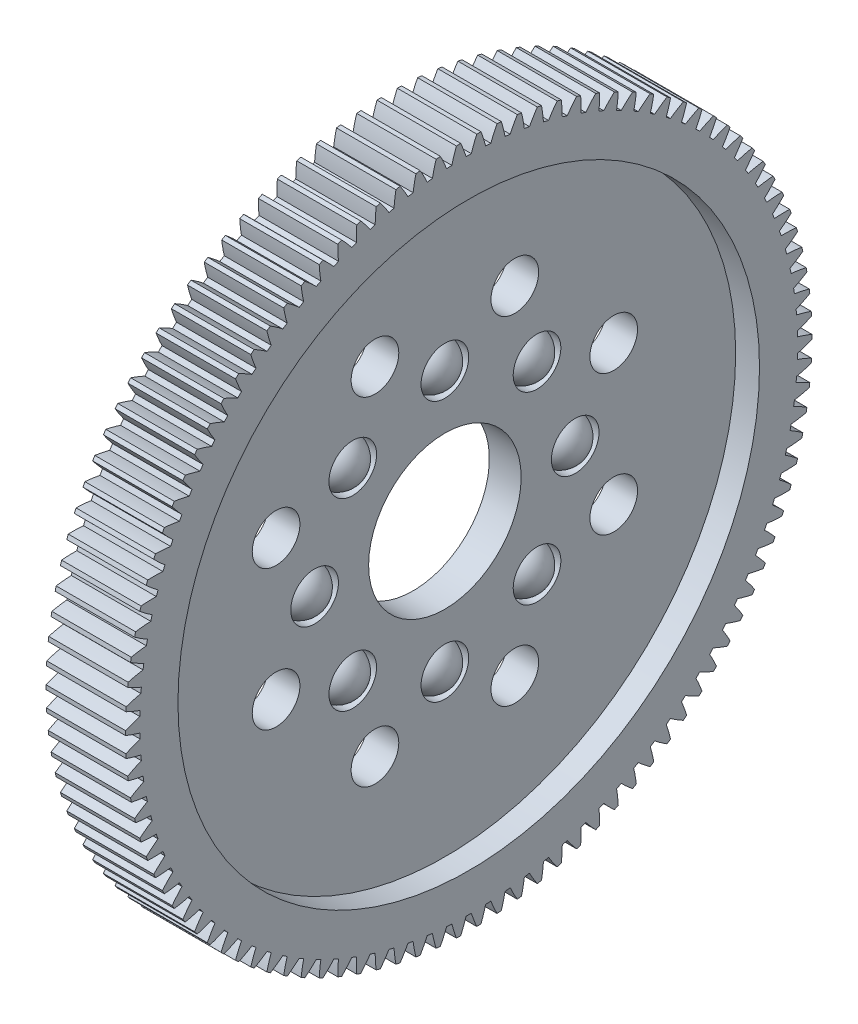
SolidWorks part; units mm, degrees
ref_plane "Plane1" through (0, 0, 0) normal (0, 0, 1) x (1, 0, 0)
ref_plane "Plane2" through (0, 0, 0) normal (0, 1, 0) x (1, 0, 0)
ref_plane "Plane3" through (0, 0, 0) normal (1, 0, 0) x (0, 0, -1)
sketch "HoldingSke" plane through (0, 0, 0) normal (0, 1, 0) x (1, 0, 0)
  line L0 (0, 0) -> (-0.6891, -2.4032)
  line L1 (-15, 0) -> (100, 0) construction
  line L2 (0, 0) -> (-2.1039, 2.3779)
  line L3 (0, 0) -> (-11.863, 4.5341)
  line L4 (0, 0) -> (-2.3804, 8.3015)
  line L5 (0, 0) -> (-46.8476, -17.4728)
  line L6 (0, 0) -> (-4.1448, -2.7965)
  line L7 (-2.1039, 2.3779) -> (8.6586, 51.2059)
  line L8 (-76.2, 54.61) -> (-76.1, 54.61)
  line L9 (-71.009, 38.7566) -> (-53.1078, 45.2721)
  line L10 (-76.2, 71.12) -> (104.1128, 71.12)
  line L11 (0, 0) -> (-5, 0)
  line L12 (-76.2, 101.6) -> (-76.185, 101.6)
  line L13 (24.9733, 27.94) -> (52.9518, 28.4284)
  line L14 (24.9733, 27.94) -> (24.9743, 27.94)
  line L15 (24.9733, 27.94) -> (100.4006, 29.5858)
  line L16 (-63.627, -0.4) -> (-12.827, -0.4)
  circle A0 centre (0, 0) radius 0.4
  circle A1 centre (0, 0) radius 20.699
  circle A2 centre (0, 0) radius 37.5
  circle A3 centre (0, 0) radius 0.4
  dimension "MHD" = 41.398
  dimension "Hub_dia" = 75
  dimension "Bore" = 0.8
  dimension "MBD" = 0.8
  dimension "Num_teeth" = 106
  dimension "Pitch_radius" = 180.3128
  dimension "Pitch" = 2.5
  dimension "Width" = 5
  dimension "Overall_len" = 50
  dimension "Show_teeth" = 106
  dimension "Thickness" = 5
  dimension "OAL" = 50.0001
  dimension "T_dim" = 0.1
  dimension "Ap" = 20
  dimension "H" = 19.05
  dimension "Backlash" = 0.015
  dimension "Addendum_fac" = 1
  dimension "Dedendum_fac" = 1.25
  dimension "Clearance_fac" = 0.25
  dimension "Dedendum_add" = 0.001
  dimension "Module" = 0.4
sketch "BasProSke" plane through (0, 0, 0) normal (0, 1, 0) x (1, 0, 0)
  line L0 (-10, 0) -> (60, 0) construction
  line L1 (0, 0) -> (0, 21.6)
  line L2 (0, 0) -> (5, 0)
  line L3 (5, 0) -> (5, 21.6)
  line L4 (5, 21.6) -> (0, 21.6)
  dimension "Diameter" = 43.2
  dimension "Thickness" = 5
revolve "Base-Revolve" add sketch "BasProSke" angle 360 about L0
sketch "TooCutSke" plane through (0, 0, 0) normal (1, 0, 0) x (0, 0, -1)
  line L1 (0, 0) -> (0, 107) construction
  line L2 (0, 0) -> (-0.3404, 21.1973) construction
  line L3 (0, 0) -> (-1.2563, 42.3775) construction
  line L4 (-0.3404, 21.1973) -> (-0.6282, 21.1887) construction
  arc A0 (0.1648, 20.6983) -> (-0.1648, 20.6983) centre (0, 0) ccw
  arc A1 (0.5171, 21.6192) -> (-0.5171, 21.6192) centre (0, 0) ccw
  circle A2 centre (0, 0) radius 21.2 construction
  circle A3 centre (0, 0) radius 19.9215 construction
  arc A4 (-0.1648, 20.6983) -> (-0.5171, 21.6192) centre (-8.2478, 18.1339) ccw
  arc A5 (0.5171, 21.6192) -> (0.1648, 20.6983) centre (8.2478, 18.1339) ccw
  dimension "Root_dia" = 41.398
  dimension "Overcut_dia" = 43.2508
  dimension "Pitch_dia" = 42.4
  dimension "Base_dia" = 39.843
  dimension "Flank_rad" = 8.48
  dimension "Half_ang" = 1.698
  dimension "Half_CT" = 0.2879
extrude "ToothCut" cut sketch "TooCutSke" along normal through all
fillet "Breaks" [suppressed] radius 0.008 tangent propagation no
fillet "RootFillets" [suppressed] radius 0.101
pattern_circular "TeethCuts" count 106 over 360 about axis through (-10, 0, 0) along (1, 0, 0) of "ToothCut", "RootFillets", "Breaks"
sketch "HubNeaOneSke" plane through (0, 0, 0) normal (-1, 0, 0) x (0, 0, 1)
  circle A0 centre (0, 0) radius 20.699
  dimension "Diameter" = 41.398
extrude "HubNearOne" [suppressed] add sketch "HubNeaOneSke" along normal blind 45.0001
sketch "HubNeaBotSke" plane through (0, 0, 0) normal (-1, 0, 0) x (0, 0, 1)
  circle A0 centre (0, 0) radius 20.699
  dimension "Diameter" = 41.398
extrude "HubNearBoth" [suppressed] add sketch "HubNeaBotSke" along normal blind 22.5
ref_plane "FarPln" through (5, 0, 0) normal (1, 0, 0) x (0, 0, -1)
sketch "HubFarSke" plane through (5, 0, 0) normal (1, 0, 0) x (0, 0, -1)
  circle A0 centre (0, 0) radius 20.699
  dimension "Diameter" = 41.398
extrude "HubFar" [suppressed] add sketch "HubFarSke" along normal blind 22.5
sketch "BorSke" plane through (0, 0, 0) normal (1, 0, 0) x (0, 0, -1)
  circle A0 centre (0, 0) radius 4.8
  dimension "Diameter" = 9.6
extrude "Bore" cut sketch "BorSke" along normal mid plane 100.0001
sketch "KeySke" plane through (0, 0, 0) normal (1, 0, 0) x (0, 0, -1)
  line L0 (-0.05, 0) -> (-0.05, 0.5)
  line L1 (-0.05, 0.5) -> (0.05, 0.5)
  line L2 (0.05, 0.5) -> (0.05, 0)
  line L3 (0, 0) -> (0, 34) construction
  line L4 (-0.05, 0) -> (0.05, 0)
  dimension "Offset" = 0.5
  dimension "Width" = 0.1
extrude "Keyway" [suppressed] cut sketch "KeySke" along normal mid plane 100.0001
pattern_circular "Keyway2" [suppressed] count 2 every 90 about axis through (-10, 0, 0) along (1, 0, 0)
ref_plane "Plane4" through (2.5, 0, 0) normal (1, 0, 0) x (0, 0, -1)
ref_axis "Axis1" through (-80.9, 0, 0) along (1, 0, 0)
sketch "Sketch2" plane through (5, 0, 0) normal (1, 0, 0) x (0, 0, -1)
  circle A0 centre (0, 0) radius 18.3
  dimension "D1" = 36.6
extrude "Cut-Extrude1" cut sketch "Sketch2" against normal blind 1.5
mirror "Mirror1" about plane through (2.5, 0, 0) normal (1, 0, 0) of "Cut-Extrude1"
sketch "Sketch3" plane through (2.5, 0, 0) normal (1, 0, 0) x (0, 0, -1)
  line L0 (0, 0) -> (0, 13.0334) construction
  line L1 (0, 0) -> (-5.791, 13.9807) construction
  circle A1 centre (0, 8.2) radius 1.5
  circle A2 centre (5.7983, 5.7983) radius 1.5
  circle A3 centre (8.2, 0) radius 1.5
  circle A4 centre (5.7983, -5.7983) radius 1.5
  circle A5 centre (0, -8.2) radius 1.5
  circle A6 centre (-5.7983, -5.7983) radius 1.5
  circle A7 centre (-8.2, 0) radius 1.5
  circle A8 centre (-5.7983, 5.7983) radius 1.5
  circle A9 centre (-4.4009, 10.6246) radius 1.5
  circle A10 centre (4.4009, 10.6246) radius 1.5
  circle A11 centre (10.6246, 4.4009) radius 1.5
  circle A12 centre (10.6246, -4.4009) radius 1.5
  circle A13 centre (4.4009, -10.6246) radius 1.5
  circle A14 centre (-4.4009, -10.6246) radius 1.5
  circle A15 centre (-10.6246, -4.4009) radius 1.5
  circle A16 centre (-10.6246, 4.4009) radius 1.5
  point P22 (0, 0)
  point P40 (0, 0)
  dimension "D3" = 3
  dimension "D6" = 3
  dimension "D2" = 8.2
  dimension "D5" = 22.5
  dimension "D7" = 11.5
  dimension "D4" = 8
  dimension "D8" = 8
extrude "Cut-Extrude2" cut sketch "Sketch3" against normal up to next and the other way up to next
sketch "Sketch4" plane through (2.5, 0, 0) normal (1, 0, 0) x (0, 0, -1)
  line L0 (0, 9.701) -> (0, 6.699)
  arc A0 (0, 6.699) -> (0, 9.701) centre (0, 8.2) ccw
  dimension "D1" = 1.501
revolve "Revolve1" add sketch "Sketch4" angle 360 about L0
pattern_circular "CirPattern3" count 8 over 360 about axis through (-80.9, 0, 0) along (1, 0, 0) of "Revolve1"
equation "' \"Module@HoldingSke\" = 6.35"
equation "' \"Num_teeth@HoldingSke\" = 12"
equation "' \"Ap@HoldingSke\" =  20"
equation "' \"Width@HoldingSke\" = 0.5 * 25.4"
equation "' \"Hub_dia@HoldingSke\"= 1 * 25.4"
equation "' \"Overall_len@HoldingSke\" = 1.0 * 25.4"
equation "' \"Bore@HoldingSke\" = 0.75 * 25.4"
equation "' \"T_dim@HoldingSke\" = 0.1 * 25.4"
equation "' \"Width@KeySke\" = 0.25 * 25.4"
equation "' \"Show_teeth@HoldingSke\" = 13"
equation "' \"Backlash@HoldingSke\" = 0.009 * 25.4"
equation "' \"Addendum_fac@HoldingSke\" = 1.0"
equation "' \"Dedendum_fac@HoldingSke\" = 1.25"
equation "' \"Dedendum_add@HoldingSke\" = 0.00005 * 25.4"
equation "' \"Clearance_fac@HoldingSke\" = 0.25"
equation "\"Pitch@HoldingSke\" = 1 / \"Module@HoldingSke\""
equation "\"Overcut_dia@TooCutSke\" = (\"Num_teeth@HoldingSke\" + 2 * \"Addendum_fac@HoldingSke\") / \"Pitch@HoldingSke\" + 0.002 * 25.4"
equation "\"Pitch_dia@TooCutSke\" = \"Num_teeth@HoldingSke\" / \"Pitch@HoldingSke\""
equation "\"Base_dia@TooCutSke\" = \"Num_teeth@HoldingSke\" / \"Pitch@HoldingSke\" * cos((\"Ap@HoldingSke\"  * 3.14159265 / 180))"
equation "\"Root_dia@TooCutSke\" = (\"Num_teeth@HoldingSke\" + 2) / \"Pitch@HoldingSke\" - 2 * (\"Addendum_fac@HoldingSke\" + \"Dedendum_fac@HoldingSke\") / \"Pitch@HoldingSke\" - \"Dedendum_add@HoldingSke\" * 2"
equation "\"Half_ang@TooCutSke\" = 180 / \"Num_teeth@HoldingSke\""
equation "\"Half_CT@TooCutSke\" = \"Num_teeth@HoldingSke\" / \"Pitch@HoldingSke\" * sin((3.14159265 / 2 / \"Num_teeth@HoldingSke\")) / 2 - 7 * \"Backlash@HoldingSke\" / 4"
equation "\"Flank_rad@TooCutSke\" = \"Num_teeth@HoldingSke\" / \"Pitch@HoldingSke\" / 5"
equation "\"Radius@RootFillets\" = \"Clearance_fac@HoldingSke\" / \"Pitch@HoldingSke\" + \"Dedendum_add@HoldingSke\""
equation "\"Break_rad@Breaks\" = 0.02 / \"Pitch@HoldingSke\""
equation "\"Thickness@HoldingSke\" = \"Width@HoldingSke\""
equation "\"OAL@HoldingSke\" = \"Thickness@HoldingSke\""
equation "\"MHD@HoldingSke\" = (\"Num_teeth@HoldingSke\" + 2) / \"Pitch@HoldingSke\" - 2 * (\"Addendum_fac@HoldingSke\" + \"Dedendum_fac@HoldingSke\")  / \"Pitch@HoldingSke\" - \"Dedendum_add@HoldingSke\" * 2"
equation "\"MBD@HoldingSke\" = (\"Num_teeth@HoldingSke\" + 2) / \"Pitch@HoldingSke\" - 2 * (\"Addendum_fac@HoldingSke\" + \"Dedendum_fac@HoldingSke\")  / \"Pitch@HoldingSke\" - \"Dedendum_add@HoldingSke\" * 2 - 0.002 * 25.4"
equation "\"MHD@HoldingSke\" = ((sgn( \"MHD@HoldingSke\" - \"Hub_dia@HoldingSke\" )-1)*( \"MHD@HoldingSke\" - \"Hub_dia@HoldingSke\" ))/-2+ \"Hub_dia@HoldingSke\""
equation "\"MBD@HoldingSke\" = ((sgn( \"MBD@HoldingSke\" - \"Bore@HoldingSke\" )-1)*( \"MBD@HoldingSke\" - \"Bore@HoldingSke\" ))/-2+ \"Bore@HoldingSke\""
equation "\"OAL@HoldingSke\" = ((sgn( \"OAL@HoldingSke\" - \"Overall_len@HoldingSke\" )+1)*( \"OAL@HoldingSke\" - \"Overall_len@HoldingSke\" ))/2 + \"Overall_len@HoldingSke\" + 0.000002 * 25.4"
equation "\"Num_teeth@TeethCuts\" = int( \"Show_teeth@HoldingSke\" ) + 1"
equation "\"Num_teeth@TeethCuts\" = ((sgn( \"Num_teeth@TeethCuts\" - \"Num_teeth@HoldingSke\" )-1)*( \"Num_teeth@TeethCuts\" - \"Num_teeth@HoldingSke\" ))/-2+ \"Num_teeth@HoldingSke\""
equation "\"Num_teeth@TeethCuts\" = ((sgn( \"Num_teeth@TeethCuts\" - 2.0)+1)*( \"Num_teeth@TeethCuts\" - 2.0))/2 +2.0"
equation "\"Angle@TeethCuts\" = 360.0 / \"Num_teeth@HoldingSke\""
equation "\"Diameter@BasProSke\" = (\"Num_teeth@HoldingSke\" + 2 * \"Addendum_fac@HoldingSke\") / \"Pitch@HoldingSke\""
equation "\"Thickness@BasProSke\"  = \"Thickness@HoldingSke\""
equation "' \"Fillet_rad@BasProSke\" =  \"Thickness@HoldingSke\" * 0.05"
equation "\"MHD@HoldingSke\" = ((sgn( \"MHD@HoldingSke\" - \"Root_dia@TooCutSke\" )-1)*( \"MHD@HoldingSke\" - \"Root_dia@TooCutSke\" ))/-2+ \"Root_dia@TooCutSke\""
equation "\"Diameter@HubNeaOneSke\" = \"MHD@HoldingSke\""
equation "\"Length@HubNearOne\" = \"OAL@HoldingSke\" - \"Thickness@BasProSke\""
equation "\"Diameter@HubNeaBotSke\" = \"MHD@HoldingSke\""
equation "\"Length@HubNearBoth\" = ( \"OAL@HoldingSke\" - \"Thickness@BasProSke\" ) / 2.0"
equation "\"Thickness@FarPln\" = \"Thickness@BasProSke\""
equation "\"Diameter@HubFarSke\" = \"MHD@HoldingSke\""
equation "\"Length@HubFar\" = ( \"OAL@HoldingSke\" - \"Thickness@BasProSke\" ) / 2.0"
equation "\"Diameter@BorSke\"=9.6"
equation "\"D1@Bore\" = \"OAL@HoldingSke\" * 2.0"
equation "\"D1@Keyway\" = \"OAL@HoldingSke\" * 2.0"
equation "\"Offset@KeySke\" = \"T_dim@HoldingSke\" + \"MBD@HoldingSke\" / 2.0"
